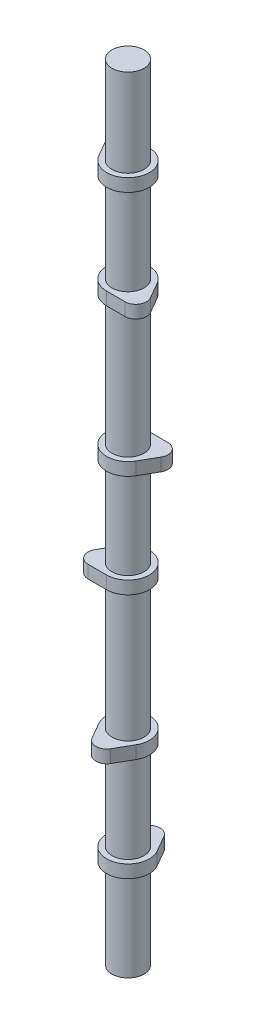
SolidWorks part; units mm, degrees
ref_plane "Front Plane" through (0, 0, 0) normal (0, 0, 1) x (1, 0, 0)
ref_plane "Top Plane" through (0, 0, 0) normal (0, 1, 0) x (1, 0, 0)
ref_plane "Right Plane" through (0, 0, 0) normal (1, 0, 0) x (0, 0, -1)
sketch "Sketch2" plane through (0, 0, 0) normal (0, 1, 0) x (1, 0, 0)
  circle A0 centre (0, 0) radius 9.5
  dimension "D1" = 19
sketch "Sketch1" plane through (0, 0, 0) normal (0, 1, 0) x (1, 0, 0)
  line L0 (-5.4993, 15.875) -> (-10.9985, 6.35)
  line L1 (5.4993, 15.875) -> (10.9985, 6.35)
  arc A0 (-10.9985, 6.35) -> (10.9985, 6.35) centre (0, 0) ccw
  arc A1 (5.4993, 15.875) -> (-5.4993, 15.875) centre (0, 12.7) ccw
  dimension "D1" = 25.4
  dimension "D2" = 12.7
  dimension "D3" = 12.7
extrude "Boss-Extrude4" add sketch "Sketch1" along normal blind 7.62
ref_axis "Axis2" through (0, 7.62, 0) along (0, -1, 0)
move or copy body "Body-Move/Copy3" bodies to move or copy 106 copy yes number of copies 1 translate (0, 60.96, 0)
move or copy body "Body-Move/Copy4" bodies to move or copy 107 copy no rotation origin (0, 0, 0) rotation axis (0, 1, 0) rotation angle 180
extrude "Boss-Extrude5" add sketch "Sketch2" along normal blind 146.02 from offset 25.4 contours A0 offset against normal yes
pattern_linear "LPattern1" count 3 spacing 146.02 along (0, 1, 0) of bodies 109
move or copy body "Body-Move/Copy5" bodies to move or copy 110 copy no rotation origin (0, 0, 0) rotation axis (0, 1, 0) rotation angle 120
move or copy body "Body-Move/Copy6" bodies to move or copy 111 copy no rotation origin (0, 0, 0) rotation axis (0, -1, 0) rotation angle 120
sketch "Sketch4" plane through (0, -25.4, 0) normal (0, -1, 0) x (1, 0, 0)
  circle A1 centre (0, 0) radius 9.5
  circle A2 centre (0, 0) radius 9.5
  dimension "D1" = 0
extrude "Boss-Extrude6" add sketch "Sketch4" along normal blind 27.92
combine bodies "Combine1" operation type add bodies to combine 113 112 114
equation "\"offset\"=25.4"
